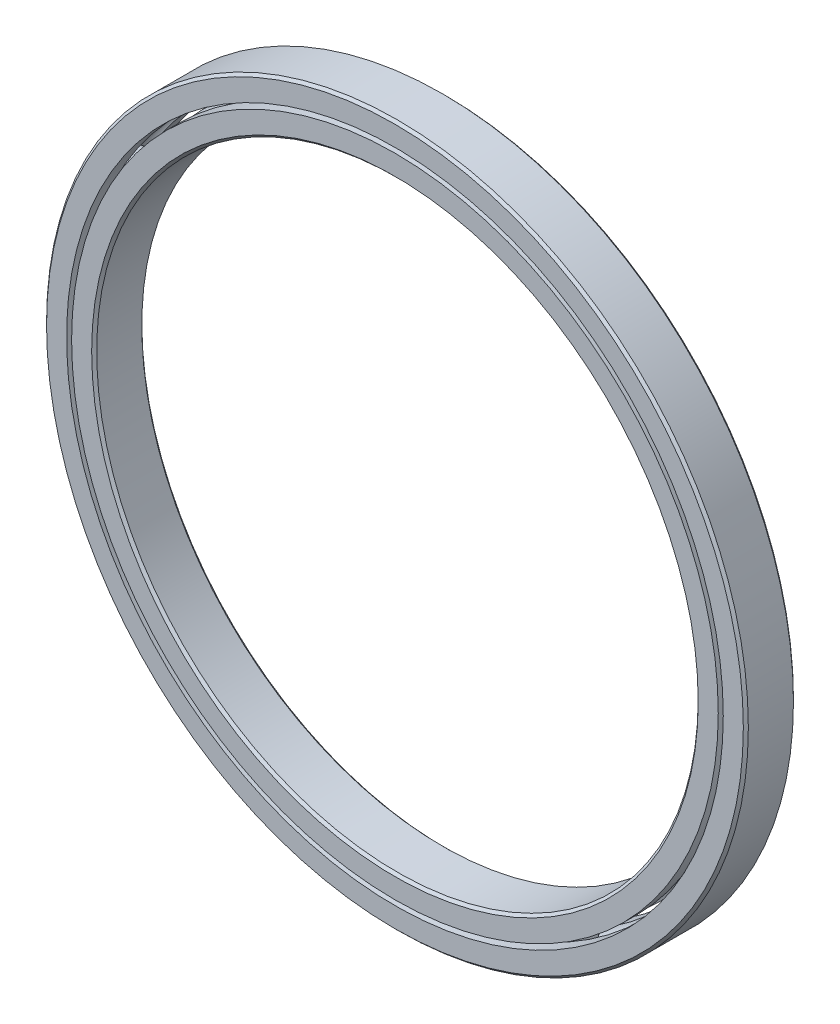
SolidWorks part; units mm, degrees
ref_plane "Front Plane" through (0, 0, 0) normal (0, 0, 1) x (1, 0, 0)
ref_plane "Top Plane" through (0, 0, 0) normal (0, 1, 0) x (1, 0, 0)
ref_plane "Right Plane" through (0, 0, 0) normal (1, 0, 0) x (0, 0, -1)
sketch "Sketch1" plane through (0, 0, 0) normal (1, 0, 0) x (0, 0, -1)
  line L0 (-3.175, 0) -> (3.175, 0) construction
  line L1 (0, 44.45) -> (0, -44.45) construction
  line L2 (2.8575, 44.45) -> (-2.8575, 44.45)
  line L3 (-2.8575, 44.45) -> (-3.175, 44.1325)
  line L4 (-3.175, 44.1325) -> (-3.175, 41.5925)
  line L5 (-3.175, 41.5925) -> (-1.4111, 41.5925)
  line L6 (3.175, 41.5925) -> (1.4111, 41.5925)
  line L7 (3.175, 44.1325) -> (3.175, 41.5925)
  line L8 (2.8575, 44.45) -> (3.175, 44.1325)
  line L9 (0, 44.45) -> (0, 41.275) construction
  line L10 (0, 41.275) -> (0, 38.1) construction
  arc A0 (-1.4111, 41.5925) -> (1.4111, 41.5925) centre (0, 41.275) cw
  point P14 (0, 38.1)
  dimension "Width" = 6.35
  dimension "OD" = 88.9
  dimension "D1" = 45
  dimension "D2" = 0.3175
  dimension "Shaft Dia" = 76.2
  dimension "D3" = 2.8222
  dimension "D4" = 0.3175
revolve "Revolve1" add sketch "Sketch1" angle 360 about L0
sketch "Sketch3" plane through (0, 0, 0) normal (1, 0, 0) x (0, 0, -1)
  line L0 (-3.175, 40.9575) -> (-1.4111, 40.9575)
  line L1 (0, 44.45) -> (0, -44.45) construction
  line L2 (-3.175, 44.1325) -> (-3.175, 41.5925) construction
  line L3 (-3.175, 40.9575) -> (-3.175, 38.4175)
  line L4 (-2.8575, 44.45) -> (-3.175, 44.1325) construction
  line L5 (-3.175, 38.4175) -> (-2.8575, 38.1)
  line L6 (-2.8575, 38.1) -> (2.8575, 38.1)
  line L7 (2.8575, 44.45) -> (2.8575, -44.45) construction
  line L8 (2.8575, 38.1) -> (3.175, 38.4175)
  line L9 (3.175, -44.1325) -> (3.175, 44.1325) construction
  line L10 (3.175, 38.4175) -> (3.175, 40.9575)
  line L11 (3.175, 40.9575) -> (1.4111, 40.9575)
  line L13 (2.8575, 44.45) -> (3.175, 44.1325) construction
  arc A0 (1.4111, 41.5925) -> (-1.4111, 41.5925) centre (0, 41.275) ccw construction
  arc A1 (1.4111, 40.9575) -> (-1.4111, 40.9575) centre (0, 41.275) cw
revolve "Revolve3" add sketch "Sketch3" angle 360 about L0
sketch "Sketch4" plane through (0, 0, 0) normal (1, 0, 0) x (0, 0, -1)
  line L0 (-1.4464, 41.275) -> (1.4464, 41.275)
  arc A2 (-1.4464, 41.275) -> (1.4464, 41.275) centre (0, 41.275) cw
  arc A3 (1.4111, 41.5925) -> (-1.4111, 41.5925) centre (0, 41.275) ccw construction
revolve "Revolve4" add sketch "Sketch4" angle 360 about L0
ref_axis "Axis1" through (0, 0, -3.175) along (0, 0, 1)
pattern_circular "CirPattern1" count 12 every 30 about axis through (0, 0, -3.175) along (0, 0, 1) of bodies 104
equation "\"D2@Sketch1\" = \"Width@Sketch1\"*.05"
equation "\"D3@Sketch1\" = \"Width@Sketch1\"/2.25"
equation "\"D4@Sketch1\" = (((\"OD@Sketch1\"-\"Width@Sketch1\")/2)/3.25)*.025"
equation "\"D2@CirPattern1\" = 360/\"Balls@CirPattern1\""
